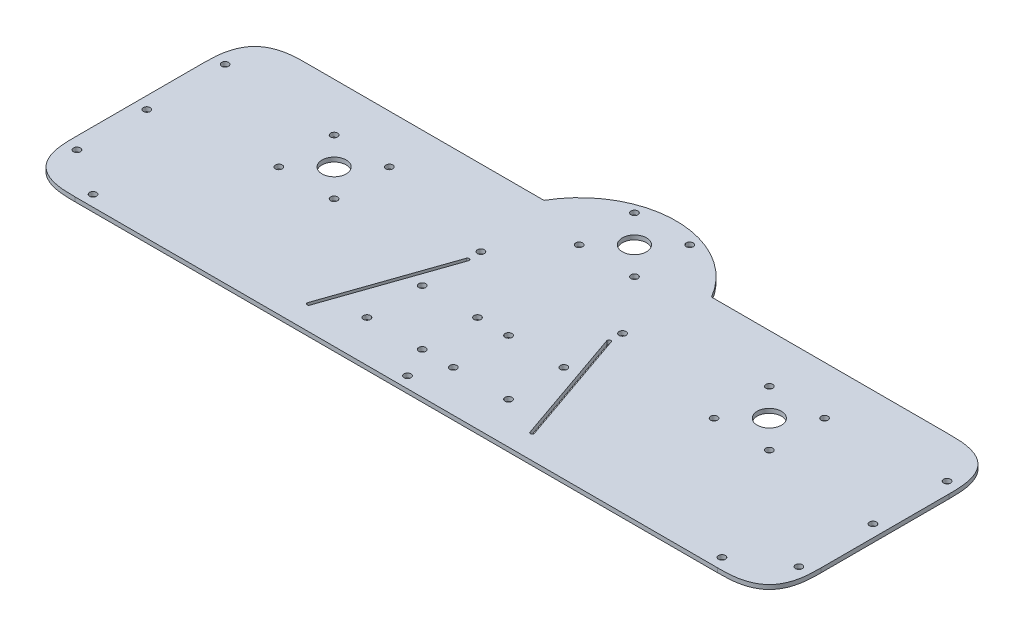
SolidWorks part; units mm, degrees
ref_plane "Front Plane" through (0, 0, 0) normal (0, 0, 1) x (1, 0, 0)
ref_plane "Top Plane" through (0, 0, 0) normal (0, 1, 0) x (1, 0, 0)
ref_plane "Right Plane" through (0, 0, 0) normal (1, 0, 0) x (0, 0, -1)
sketch "Sketch1" plane through (0, 0, 0) normal (0, 1, 0) x (1, 0, 0)
  line L1 (-103.134, 171.9149) -> (328.866, 171.9149)
  line L2 (-103.134, 171.9149) -> (-103.134, -28.0851)
  line L3 (-103.134, -28.0851) -> (328.866, -28.0851)
  line L4 (328.866, 171.9149) -> (328.866, -28.0851)
extrude "Boss-Extrude1" add sketch "Sketch1" along normal blind 2.5 contours L1 L4 L3 L2
sketch "Sketch3" plane through (0, 2.5, 0) normal (0, 1, 0) x (1, 0, 0)
  line L0 (-13.134, 71.9149) -> (-29.1359, 55.9131)
  line L1 (2.8678, 87.9167) -> (-29.1359, 87.9167)
  line L2 (2.8678, 87.9167) -> (2.8678, 55.9131)
  line L3 (2.8678, 55.9131) -> (-29.1359, 55.9131)
  line L4 (-29.1359, 87.9167) -> (-29.1359, 55.9131)
  line L5 (2.8678, 87.9167) -> (-29.1359, 55.9131) construction
  line L6 (2.8678, 55.9131) -> (-29.1359, 87.9167) construction
  line L7 (-103.134, 71.9149) -> (-13.134, 71.9149)
  line L8 (-103.134, 171.9149) -> (-103.134, -28.0851) construction
  line L9 (238.866, 71.9149) -> (238.866, 115.9149)
  line L14 (62.253, -0.3819) -> (46.2512, -16.3837)
  line L15 (238.866, 115.9149) -> (328.866, 115.9149)
  line L18 (328.866, 171.9149) -> (328.866, -28.0851) construction
  line L19 (238.866, 71.9149) -> (222.8641, 55.9131)
  line L20 (254.8678, 87.9167) -> (222.8641, 87.9167)
  line L21 (254.8678, 87.9167) -> (254.8678, 55.9131)
  line L22 (254.8678, 55.9131) -> (222.8641, 55.9131)
  line L23 (222.8641, 87.9167) -> (222.8641, 55.9131)
  line L24 (254.8678, 87.9167) -> (222.8641, 55.9131) construction
  line L25 (254.8678, 55.9131) -> (222.8641, 87.9167) construction
  line L27 (328.866, 71.9149) -> (238.866, 71.9149)
  line L28 (238.866, 115.9149) -> (238.866, 171.9149)
  line L29 (238.866, 171.9149) -> (328.866, 171.9149)
  line L30 (328.866, 115.9149) -> (328.866, 171.9149)
  line L31 (328.866, 115.9149) -> (-169.3435, 115.9149)
  line L32 (328.866, 115.9149) -> (328.866, 173.2785)
  line L33 (328.866, 173.2785) -> (-169.3435, 173.2785)
  line L34 (-169.3435, 115.9149) -> (-169.3435, 173.2785)
  line L35 (78.2549, 15.6199) -> (46.2512, 15.6199)
  line L36 (78.2549, 15.6199) -> (78.2549, -16.3837)
  line L37 (78.2549, -16.3837) -> (46.2512, -16.3837)
  line L38 (46.2512, 15.6199) -> (46.2512, -16.3837)
  line L39 (78.2549, 15.6199) -> (46.2512, -16.3837) construction
  line L40 (78.2549, -16.3837) -> (46.2512, 15.6199) construction
  circle A0 centre (-13.134, 71.9149) radius 7
  circle A1 centre (-29.1359, 55.9131) radius 2
  circle A2 centre (-29.1359, 87.9167) radius 2
  circle A3 centre (2.8678, 87.9167) radius 2
  circle A4 centre (2.8678, 55.9131) radius 2
  circle A10 centre (238.866, 71.9149) radius 7
  circle A11 centre (222.8641, 55.9131) radius 2
  circle A12 centre (222.8641, 87.9167) radius 2
  circle A13 centre (254.8678, 87.9167) radius 2
  circle A14 centre (254.8678, 55.9131) radius 2
  circle A15 centre (62.253, -0.3819) radius 7
  circle A16 centre (46.2512, -16.3837) radius 2
  circle A17 centre (46.2512, 15.6199) radius 2
  circle A18 centre (78.2549, 15.6199) radius 2
  circle A19 centre (78.2549, -16.3837) radius 2
  point P10 (328.866, 71.9149)
extrude "Cut-Extrude1" cut sketch "Sketch3" against normal blind 2.5 contours A2 | A3 | A4 | A1 | A0 | A11 | A14 | A13 | A10 | A12 | L32 L31 L34 L33
sketch "Sketch5" plane through (0, 2.5, 0) normal (0, 1, 0) x (1, 0, 0)
  line L0 (263.7413, -28.0851) -> (263.7413, -18.0851)
  line L3 (-103.134, -28.0851) -> (328.866, -28.0851) construction
  line L5 (263.7413, -18.0851) -> (328.866, -18.0851)
  line L6 (263.7413, -18.0851) -> (263.7413, -28.0851)
  line L7 (263.7413, -28.0851) -> (328.866, -28.0851)
  line L8 (328.866, -18.0851) -> (328.866, -28.0851)
  line L9 (263.7413, -18.0851) -> (-103.134, -18.0851)
  line L10 (263.7413, -18.0851) -> (263.7413, -28.0851)
  line L11 (263.7413, -28.0851) -> (-103.134, -28.0851)
  line L12 (-103.134, -18.0851) -> (-103.134, -28.0851)
  line M12 (328.866, -28.0851) -> (328.866, 115.9149)
  line M14 (-103.134, 115.9149) -> (-103.134, -28.0851)
  line M15 (-103.134, -28.0851) -> (328.866, -28.0851)
extrude "Cut-Extrude3" cut sketch "Sketch5" against normal blind 2.5 contours L0 L9 M14 M15 | L5 L0 M15 M12 region at (80.3036, 2.5, 23.0851) region at (296.3036, 2.5, 23.0851)
sketch "Sketch6" plane through (0, 2.5, 0) normal (0, 1, 0) x (1, 0, 0)
  line L0 (328.866, -18.0851) -> (-103.134, -18.0851) construction
  line L1 (112.866, -18.0851) -> (112.866, 21.9149)
  line L2 (112.866, 21.9149) -> (137.866, 21.9149)
  line L3 (112.866, 21.9149) -> (87.866, 21.9149)
  line L4 (87.866, 21.9149) -> (71.8641, 5.9131)
  line L5 (103.8678, 37.9167) -> (71.8641, 37.9167)
  line L6 (103.8678, 37.9167) -> (103.8678, 5.9131)
  line L7 (103.8678, 5.9131) -> (71.8641, 5.9131)
  line L8 (71.8641, 37.9167) -> (71.8641, 5.9131)
  line L9 (103.8678, 37.9167) -> (71.8641, 5.9131) construction
  line L10 (103.8678, 5.9131) -> (71.8641, 37.9167) construction
  line L11 (137.866, 21.9149) -> (121.8641, 5.9131)
  line L12 (153.8678, 37.9167) -> (121.8641, 37.9167)
  line L13 (153.8678, 37.9167) -> (153.8678, 5.9131)
  line L14 (153.8678, 5.9131) -> (121.8641, 5.9131)
  line L15 (121.8641, 37.9167) -> (121.8641, 5.9131)
  line L16 (153.8678, 37.9167) -> (121.8641, 5.9131) construction
  line L17 (153.8678, 5.9131) -> (121.8641, 37.9167) construction
  circle A0 centre (137.866, 21.9149) radius 16
  circle A1 centre (87.866, 21.9149) radius 16
  circle A2 centre (87.866, 21.9149) radius 7
  circle A3 centre (71.8641, 5.9131) radius 2
  circle A4 centre (71.8641, 37.9167) radius 2
  circle A5 centre (103.8678, 37.9167) radius 2
  circle A6 centre (103.8678, 5.9131) radius 2
  circle A7 centre (137.866, 21.9149) radius 7
  circle A8 centre (121.8641, 5.9131) radius 2
  circle A9 centre (121.8641, 37.9167) radius 2
  circle A10 centre (153.8678, 37.9167) radius 2
  circle A11 centre (153.8678, 5.9131) radius 2
  point P0 (112.866, -18.0851)
extrude "Cut-Extrude4" cut sketch "Sketch6" against normal blind 2.5 contours A11 | A8 | A10 | A9 | A5 | A6 | A3 | A4
sketch "Sketch8" plane through (0, 2.5, 0) normal (0, 1, 0) x (1, 0, 0)
  line L2 (153.8678, 5.9131) -> (153.8678, 90.0973)
  line L3 (153.8678, 90.0973) -> (71.8641, 90.0973)
  line L4 (71.8641, 90.0973) -> (71.8641, 5.9131)
  line L5 (153.8678, 64.0929) -> (71.8641, 64.0929)
  line L10 (177.527, -4.0851) -> (153.8678, 64.0929) construction
  line L14 (176.5823, -4.4129) -> (152.9231, 63.7651)
  line L15 (178.4718, -3.7572) -> (154.8125, 64.4208)
  line L16 (48.2049, -4.0851) -> (71.8641, 64.0929) construction
  line L17 (47.2602, -3.7572) -> (70.9194, 64.4208)
  line L18 (49.1496, -4.4129) -> (72.8089, 63.7651)
  arc A6 (176.5823, -4.4129) -> (178.4718, -3.7572) centre (177.527, -4.0851) ccw
  arc A7 (154.8125, 64.4208) -> (152.9231, 63.7651) centre (153.8678, 64.0929) ccw
  arc A8 (47.2602, -3.7572) -> (49.1496, -4.4129) centre (48.2049, -4.0851) ccw
  arc A9 (72.8089, 63.7651) -> (70.9194, 64.4208) centre (71.8641, 64.0929) ccw
  point P17 (177.527, 5.9131)
  point P18 (48.2049, 5.9131)
  point P19 (165.6974, 30.0039)
  point P22 (112.866, -4.0851)
  point P27 (60.0345, 30.0039)
extrude "Cut-Extrude5" cut sketch "Sketch8" against normal blind 2.5 contours L17 A9 L18 A8 | L15 A7 L14 A6
fillet "Fillet1" radius 30 4 edges at (-103.134, 1.25, -115.9149) (-103.134, 1.25, 18.0851) (328.866, 1.25, -115.9149) (328.866, 1.25, 18.0851) curvature continuous yes
sketch "Sketch9" plane through (0, 2.5, 0) normal (0, 1, 0) x (1, 0, 0)
  line L0 (328.866, 62.6221) -> (321.866, 62.6221)
  line L1 (328.866, 85.9149) -> (328.866, 11.9149) construction
  line L2 (321.866, 109.7214) -> (321.866, -11.8915)
  line L3 (321.866, 6.0103) -> (321.866, -11.8915)
  line L4 (321.866, 109.7214) -> (321.866, 91.8196)
  line L5 (321.866, 91.8196) -> (321.866, 109.7214)
  line L6 (-103.134, 46.4673) -> (-96.134, 46.4673)
  line L7 (-103.134, 85.9149) -> (-103.134, 11.9149) construction
  line L8 (-96.134, 46.4673) -> (-96.134, 109.7214)
  line L9 (-96.134, 109.7214) -> (-96.134, -11.8916)
  line L10 (-96.134, -11.8916) -> (-96.134, 6.0103)
  line L11 (-96.134, 109.7214) -> (-96.134, 97.3154)
  line L12 (-96.134, 109.7214) -> (-96.134, 91.8196)
  circle A0 centre (321.866, 6.0103) radius 2
  circle A1 centre (321.866, 48.9149) radius 2
  circle A2 centre (321.866, 91.8196) radius 2
  circle A3 centre (-96.134, 46.4673) radius 2
  circle A4 centre (-96.134, 91.8196) radius 2
  circle A5 centre (-96.134, 6.0103) radius 2
  spline S0 degree 2 poles (328.866, 85.9149) (328.866, 87.9765) (328.8467, 89.0459) (328.8162, 90.7467) (328.7231, 92.1742) (328.5043, 95.5283) (327.8783, 98.3317) (326.3274, 105.2776) (322.2688, 109.3319) (318.2198, 113.3765) (311.2895, 114.9258) (308.4764, 115.5546) (305.1048, 115.7733) (303.6844, 115.8655) (301.9893, 115.8958) (300.9233, 115.9149) (298.866, 115.9149) knots 0 0 0 0.0625 0.0625 0.125 0.125 0.25 0.25 0.5 0.5 0.75 0.75 0.875 0.875 0.9375 0.9375 1 1 1 construction
  spline S1 degree 2 poles (298.866, -18.0851) (300.9275, -18.0851) (301.997, -18.0659) (303.6978, -18.0353) (305.1253, -17.9422) (308.4794, -17.7234) (311.2827, -17.0975) (318.2287, -15.5466) (322.283, -11.4879) (326.3276, -7.4389) (327.8768, -0.5086) (328.5057, 2.3045) (328.7244, 5.6761) (328.8165, 7.0965) (328.8469, 8.7916) (328.866, 9.8575) (328.866, 11.9149) knots 0 0 0 0.0625 0.0625 0.125 0.125 0.25 0.25 0.5 0.5 0.75 0.75 0.875 0.875 0.9375 0.9375 1 1 1 construction
  spline S2 degree 2 poles (-73.134, 115.9149) (-75.1956, 115.9149) (-76.2651, 115.8957) (-77.9658, 115.8651) (-79.3933, 115.772) (-82.7474, 115.5532) (-85.5508, 114.9273) (-92.4967, 113.3764) (-96.551, 109.3177) (-100.5957, 105.2687) (-102.1449, 98.3384) (-102.7737, 95.5254) (-102.9924, 92.1538) (-103.0846, 90.7333) (-103.1149, 89.0383) (-103.134, 87.9723) (-103.134, 85.9149) knots 0 0 0 0.0625 0.0625 0.125 0.125 0.25 0.25 0.5 0.5 0.75 0.75 0.875 0.875 0.9375 0.9375 1 1 1 construction
  spline S3 degree 2 poles (-103.134, 11.9149) (-103.134, 9.8534) (-103.1148, 8.7839) (-103.0842, 7.0831) (-102.9911, 5.6556) (-102.7723, 2.3015) (-102.1464, -0.5019) (-100.5955, -7.4478) (-96.5368, -11.5021) (-92.4879, -15.5467) (-85.5575, -17.0959) (-82.7445, -17.7248) (-79.3729, -17.9435) (-77.9525, -18.0356) (-76.2574, -18.066) (-75.1914, -18.0851) (-73.134, -18.0851) knots 0 0 0 0.0625 0.0625 0.125 0.125 0.25 0.25 0.5 0.5 0.75 0.75 0.875 0.875 0.9375 0.9375 1 1 1 construction
extrude "Cut-Extrude6" cut sketch "Sketch9" against normal blind 2.5 contours A0 | A1 | A2 | A5 | A3 | A4
sketch "Sketch10" plane through (0, 2.5, 0) normal (0, 1, 0) x (1, 0, 0)
  line L0 (232.1904, -18.0851) -> (232.1904, -11.5851)
  line L1 (298.866, -18.0851) -> (-73.134, -18.0851) construction
  line L2 (322.1851, -11.5851) -> (-96.4532, -11.5851)
  line L3 (322.1851, -11.5851) -> (232.1904, -11.5851)
  line L4 (322.1851, -11.5851) -> (232.1904, -11.5851)
  line L5 (322.1851, -11.5851) -> (232.1904, -11.5851)
  line L6 (322.1851, -11.5851) -> (294.9418, -11.5851)
  line L7 (-96.4532, -11.5851) -> (-78.7572, -11.5851)
  line L8 (-96.4532, -11.5851) -> (-69.2097, -11.5851)
  circle A0 centre (112.866, -11.5851) radius 2
  circle A3 centre (294.9418, -11.5851) radius 2
  circle A4 centre (-69.2097, -11.5851) radius 2
  spline S0 degree 2 poles (298.866, -18.0851) (300.9275, -18.0851) (301.997, -18.0659) (303.6978, -18.0353) (305.1253, -17.9422) (308.4794, -17.7234) (311.2827, -17.0975) (318.2287, -15.5466) (322.283, -11.4879) (326.3276, -7.4389) (327.8768, -0.5086) (328.5057, 2.3045) (328.7244, 5.6761) (328.8165, 7.0965) (328.8469, 8.7916) (328.866, 9.8575) (328.866, 11.9149) knots 0 0 0 0.0625 0.0625 0.125 0.125 0.25 0.25 0.5 0.5 0.75 0.75 0.875 0.875 0.9375 0.9375 1 1 1 construction
  spline S1 degree 2 poles (-103.134, 11.9149) (-103.134, 9.8534) (-103.1148, 8.7839) (-103.0842, 7.0831) (-102.9911, 5.6556) (-102.7723, 2.3015) (-102.1464, -0.5019) (-100.5955, -7.4478) (-96.5368, -11.5021) (-92.4879, -15.5467) (-85.5575, -17.0959) (-82.7445, -17.7248) (-79.3729, -17.9435) (-77.9525, -18.0356) (-76.2574, -18.066) (-75.1914, -18.0851) (-73.134, -18.0851) knots 0 0 0 0.0625 0.0625 0.125 0.125 0.25 0.25 0.5 0.5 0.75 0.75 0.875 0.875 0.9375 0.9375 1 1 1 construction
extrude "Cut-Extrude7" cut sketch "Sketch10" against normal blind 2.5 contours A4 | A0 | A3
sketch "Sketch11" plane through (0, 2.5, 0) normal (0, 1, 0) x (1, 0, 0)
  line L0 (71.8641, 37.9167) -> (71.8641, 115.9149)
  line L1 (298.866, 115.9149) -> (-73.134, 115.9149) construction
  line L2 (153.8678, 37.9167) -> (153.8678, 115.9149)
  line L3 (-13.134, 71.9149) -> (170.9876, 71.9149)
  line L4 (121.8641, 37.9167) -> (121.8641, 95.7488)
  line L5 (121.8641, 71.9149) -> (105.8623, 55.9131)
  line L6 (137.866, 87.9167) -> (105.8623, 87.9167)
  line L7 (137.866, 87.9167) -> (137.866, 55.9131)
  line L8 (137.866, 55.9131) -> (105.8623, 55.9131)
  line L9 (105.8623, 87.9167) -> (105.8623, 55.9131)
  line L10 (137.866, 87.9167) -> (105.8623, 55.9131) construction
  line L11 (137.866, 55.9131) -> (105.8623, 87.9167) construction
  circle A1 centre (121.8641, 71.9149) radius 7
  circle A3 centre (105.8623, 55.9131) radius 2
  circle A4 centre (105.8623, 87.9167) radius 2
  circle A5 centre (137.866, 87.9167) radius 2
  circle A6 centre (137.866, 55.9131) radius 2
  circle A7 centre (153.8678, 71.9149) radius 2
  circle A9 centre (71.8641, 71.9149) radius 2
extrude "Cut-Extrude8" cut sketch "Sketch11" against normal blind 10 contours A7 | A9
sketch "Sketch12" plane through (0, 2.5, 0) normal (0, 1, 0) x (1, 0, 0)
  line L0 (112.866, -9.5851) -> (112.866, 115.9149)
  line L1 (298.866, 115.9149) -> (-73.134, 115.9149) construction
  line L2 (112.866, 115.9149) -> (112.866, 119.8149)
  line L3 (112.866, 119.8149) -> (96.8641, 103.8131)
  line L4 (128.8678, 135.8167) -> (96.8641, 135.8167)
  line L5 (128.8678, 135.8167) -> (128.8678, 103.8131)
  line L6 (128.8678, 103.8131) -> (96.8641, 103.8131)
  line L7 (96.8641, 135.8167) -> (96.8641, 103.8131)
  line L8 (128.8678, 135.8167) -> (96.8641, 103.8131) construction
  line L9 (128.8678, 103.8131) -> (96.8641, 135.8167) construction
  circle A0 centre (112.866, -11.5851) radius 2 construction
  circle A1 centre (112.866, 119.8149) radius 3
  circle A3 centre (112.866, 119.8149) radius 18.75
  circle A4 centre (112.866, 119.8149) radius 7
  circle A5 centre (96.8641, 103.8131) radius 2
  circle A6 centre (96.8641, 135.8167) radius 2
  circle A7 centre (128.8678, 135.8167) radius 2
  circle A8 centre (128.8678, 103.8131) radius 2
  arc A9 (64.3675, 115.9149) -> (161.3644, 115.9149) centre (112.866, 87.9167) cw
  line M34 (298.866, 115.9149) -> (-73.134, 115.9149)
extrude "Boss-Extrude2" add sketch "Sketch12" against normal blind 2.5 contours A4 L5 A3 L4 L7 M34 | L4 A3 | A3 L5 M34 | L7 A3 M34 | A6 L7 A3 L4 | A7 L4 A3 L5 | A9 A3 L7 A6 L4 A7 L5 M34 region at (119.9232, 2.5, -117.6668) region at (130.047, 2.5, -121.5067) region at (132.5172, 2.5, -117.7486) region at (95.685, 2.5, -121.5067) region at (126.7073, 2.5, -133.6563) region at (99.0246, 2.5, -133.6563) region at (112.866, 2.5, -136.9232)
sketch "Sketch13" plane through (0, 2.5, 0) normal (0, 1, 0) x (1, 0, 0)
  line L0 (112.866, 119.8149) -> (96.8641, 103.8131)
  line L1 (128.8678, 135.8167) -> (96.8641, 135.8167)
  line L2 (128.8678, 135.8167) -> (128.8678, 103.8131)
  line L3 (128.8678, 103.8131) -> (96.8641, 103.8131)
  line L4 (96.8641, 135.8167) -> (96.8641, 103.8131)
  line L5 (128.8678, 135.8167) -> (96.8641, 103.8131) construction
  line L6 (128.8678, 103.8131) -> (96.8641, 135.8167) construction
  circle A0 centre (112.866, 119.8149) radius 18.75
  circle A1 centre (112.866, 119.8149) radius 7
  circle A2 centre (96.8641, 103.8131) radius 2
  circle A3 centre (96.8641, 135.8167) radius 2
  circle A4 centre (128.8678, 135.8167) radius 2
  circle A5 centre (128.8678, 103.8131) radius 2
  point P0 (112.866, 119.8149)
extrude "Cut-Extrude9" cut sketch "Sketch13" against normal blind 2.5 contours A5 | A1 | A2 | A3 | A4
